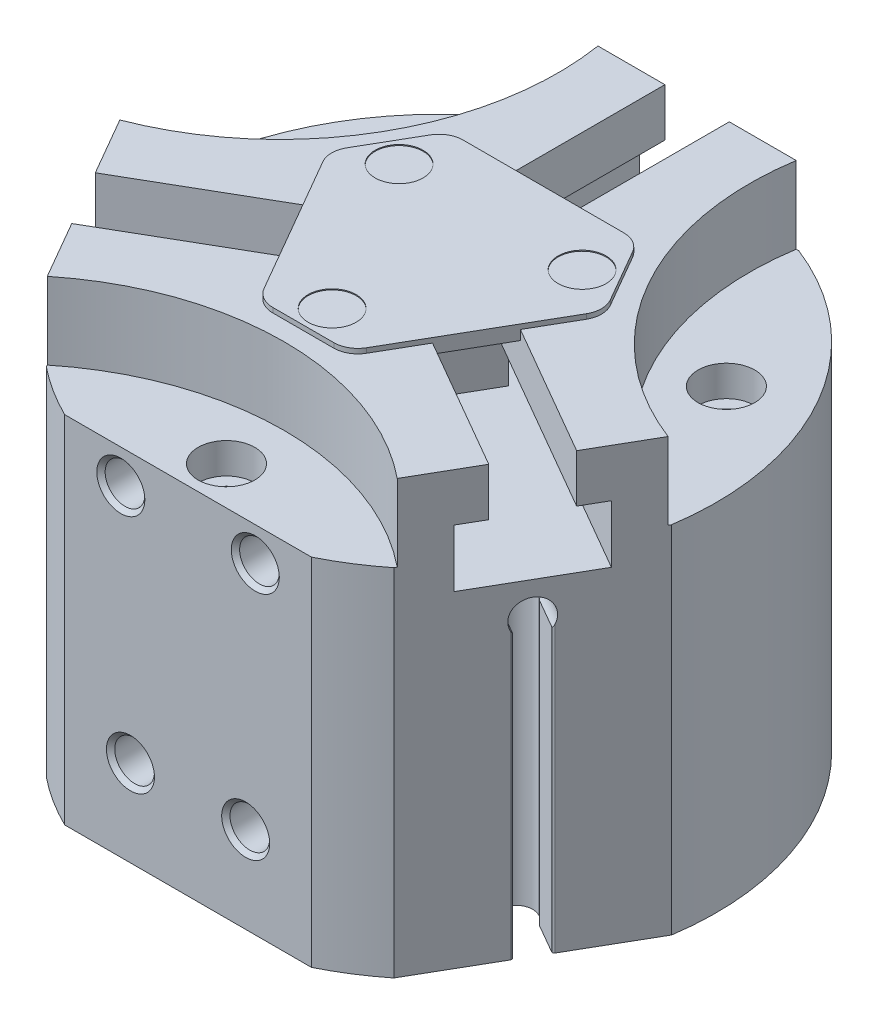
SolidWorks part; units mm, degrees
ref_plane "Front Plane" through (0, 0, 0) normal (0, 0, 1) x (1, 0, 0)
ref_plane "Top Plane" through (0, 0, 0) normal (0, 1, 0) x (1, 0, 0)
ref_plane "Right Plane" through (0, 0, 0) normal (1, 0, 0) x (0, 0, -1)
sketch "Sketch1" plane through (0, 0, 0) normal (0, 1, 0) x (1, 0, 0)
  line L0 (-28.6742, -4.3348) -> (-18.0912, -22.6652)
  line L1 (-12.8452, -26) -> (12.8452, -26)
  line L2 (18.0912, -22.6652) -> (28.6742, -4.3348)
  line L3 (10.583, 27) -> (-10.583, 27)
  arc A0 (-10.583, 27) -> (-28.6742, -4.3348) centre (0, 0) ccw
  arc A1 (-18.0912, -22.6652) -> (-12.8452, -26) centre (0, 0) ccw
  arc A2 (12.8452, -26) -> (18.0912, -22.6652) centre (0, 0) ccw
  arc A3 (28.6742, -4.3348) -> (10.583, 27) centre (0, 0) ccw
extrude "Boss-Extrude1" add sketch "Sketch1" along normal blind 45
ref_plane "Plane1" through (0, 45, 0) normal (0, 1, 0) x (1, 0, 0)
sketch "Sketch2" plane through (0, 45, 0) normal (0, 1, 0) x (1, 0, 0)
  line L0 (-34, -34) -> (34, -34)
  line L1 (34, -34) -> (34, 34)
  line L2 (34, 34) -> (-34, 34)
  line L3 (-34, 34) -> (-34, -34)
  line L4 (-30, -30) -> (-24.8193, -30)
  line L5 (24.8193, -30) -> (30, -30)
  line L6 (30, -30) -> (30, -5.0775)
  line L7 (10.9578, 30) -> (-10.9578, 30)
  line L8 (-30, -5.0775) -> (-30, -30)
  arc A0 (-24.8193, -30) -> (24.8193, -30) centre (0, -45) cw
  arc A1 (30, -5.0775) -> (10.9578, 30) centre (38.9711, 22.5) cw
  arc A2 (-10.9578, 30) -> (-30, -5.0775) centre (-38.9711, 22.5) cw
extrude "Cut-Extrude1" cut sketch "Sketch2" against normal blind 8
ref_plane "Plane2" through (0, 37, 0) normal (0, 1, 0) x (1, 0, 0)
sketch "Sketch3" plane through (0, 0, 0) normal (1, 0, 0) x (0, 0, -1)
  line L0 (-22, 37) -> (-19.05, 37)
  line L1 (-19.05, 37) -> (-19.05, 33.8)
  line L2 (-19.05, 33.8) -> (-20.35, 33.8)
  line L3 (-20.35, 33.8) -> (-20.35, 8)
  line L4 (-20.35, 8) -> (-20.379, 8)
  line L5 (-20.379, 8) -> (-20.379, 0.379)
  line L6 (-20.379, 0.379) -> (-20, 0)
  line L7 (-20, 0) -> (-22, 0)
  line L8 (-22, 0) -> (-22, 37)
  line L9 (-22, 0) -> (-22, 37) construction
revolve "Cut-Revolve1" cut sketch "Sketch3" angle 360 about L9 reverse direction yes
cosmetic thread "Cosmetic Thread1" parameters "D1"=8, "D2"=4
ref_plane "Plane3" through (19.05, 0, 0) normal (1, 0, 0) x (0, 0, -1)
sketch "Sketch4" plane through (19.05, 0, 0) normal (1, 0, 0) x (0, 0, -1)
  line L0 (11, 37) -> (13.95, 37)
  line L1 (13.95, 37) -> (13.95, 33.8)
  line L2 (13.95, 33.8) -> (12.65, 33.8)
  line L3 (12.65, 33.8) -> (12.65, 8)
  line L4 (12.65, 8) -> (12.621, 8)
  line L5 (12.621, 8) -> (12.621, 0.379)
  line L6 (12.621, 0.379) -> (13, 0)
  line L7 (13, 0) -> (11, 0)
  line L8 (11, 0) -> (11, 37)
  line L9 (11, 0) -> (11, 37) construction
revolve "Cut-Revolve2" cut sketch "Sketch4" angle 360 about L9 reverse direction yes
cosmetic thread "Cosmetic Thread2" parameters "D1"=8, "D2"=4
ref_plane "Plane4" through (-19.05, 0, 0) normal (1, 0, 0) x (0, 0, -1)
sketch "Sketch5" plane through (-19.05, 0, 0) normal (1, 0, 0) x (0, 0, -1)
  line L0 (11, 37) -> (13.95, 37)
  line L1 (13.95, 37) -> (13.95, 33.8)
  line L2 (13.95, 33.8) -> (12.65, 33.8)
  line L3 (12.65, 33.8) -> (12.65, 8)
  line L4 (12.65, 8) -> (12.621, 8)
  line L5 (12.621, 8) -> (12.621, 0.379)
  line L6 (12.621, 0.379) -> (13, 0)
  line L7 (13, 0) -> (11, 0)
  line L8 (11, 0) -> (11, 37)
  line L9 (11, 0) -> (11, 37) construction
revolve "Cut-Revolve3" cut sketch "Sketch5" angle 360 about L9 reverse direction yes
cosmetic thread "Cosmetic Thread3" parameters "D1"=8, "D2"=4
sketch "Sketch6" plane through (0, 0, 0) normal (0, 1, 0) x (1, 0, 0)
  line L0 (-1.9, 28) -> (-1.9, 27)
  line L1 (-1.9, 27) -> (-1.7, 27)
  line L2 (-1.5, 26.8) -> (-1.5, 23.3)
  line L3 (-1.6807, 23.1009) -> (-1.7, 23.0991)
  line L4 (-1.8798, 22.8816) -> (-1.7924, 21.9345)
  line L5 (1.7924, 21.9345) -> (1.8798, 22.8816)
  line L6 (1.7, 23.0991) -> (1.6807, 23.1009)
  line L7 (1.5, 23.3) -> (1.5, 26.8)
  line L8 (1.7, 27) -> (1.9, 27)
  line L9 (1.9, 27) -> (1.9, 28)
  line L10 (1.9, 28) -> (-1.9, 28)
  arc A0 (-1.7, 27) -> (-1.5, 26.8) centre (-1.7, 26.8) cw
  arc A1 (-1.5, 23.3) -> (-1.6807, 23.1009) centre (-1.7, 23.3) cw
  arc A2 (-1.7, 23.0991) -> (-1.8798, 22.8816) centre (-1.6807, 22.9) ccw
  arc A3 (-1.7924, 21.9345) -> (1.7924, 21.9345) centre (0, 22.1) ccw
  arc A4 (1.8798, 22.8816) -> (1.7, 23.0991) centre (1.6807, 22.9) ccw
  arc A5 (1.6807, 23.1009) -> (1.5, 23.3) centre (1.7, 23.3) cw
  arc A6 (1.5, 26.8) -> (1.7, 27) centre (1.7, 26.8) cw
extrude "Cut-Extrude2" cut sketch "Sketch6" along normal blind 30.5
sketch "Sketch7" plane through (0, 0, 0) normal (0, 1, 0) x (1, 0, 0)
  line L0 (-25.1987, -12.3546) -> (-23.2987, -15.6454)
  line L1 (-23.2987, -15.6454) -> (-22.4327, -15.1454)
  line L2 (-22.4327, -15.1454) -> (-22.5327, -14.9722)
  line L3 (-22.4595, -14.699) -> (-19.4284, -12.949)
  line L4 (-19.1656, -13.006) -> (-19.1544, -13.0217)
  line L5 (-18.8761, -13.0688) -> (-18.0996, -12.5195)
  line L6 (-19.892, -9.415) -> (-20.756, -9.8128)
  line L7 (-20.8544, -10.0773) -> (-20.8464, -10.0949)
  line L8 (-20.9284, -10.351) -> (-23.9595, -12.101)
  line L9 (-24.2327, -12.0278) -> (-24.3327, -11.8546)
  line L10 (-24.3327, -11.8546) -> (-25.1987, -12.3546)
  arc A0 (-22.5327, -14.9722) -> (-22.4595, -14.699) centre (-22.3595, -14.8722) cw
  arc A1 (-19.4284, -12.949) -> (-19.1656, -13.006) centre (-19.3284, -13.1222) cw
  arc A2 (-19.1544, -13.0217) -> (-18.8761, -13.0688) centre (-18.9916, -12.9055) ccw
  arc A3 (-18.0996, -12.5195) -> (-19.892, -9.415) centre (-19.1392, -11.05) ccw
  arc A4 (-20.756, -9.8128) -> (-20.8544, -10.0773) centre (-20.6723, -9.9945) ccw
  arc A5 (-20.8464, -10.0949) -> (-20.9284, -10.351) centre (-21.0284, -10.1778) cw
  arc A6 (-23.9595, -12.101) -> (-24.2327, -12.0278) centre (-24.0595, -11.9278) cw
extrude "Cut-Extrude3" cut sketch "Sketch7" along normal blind 30.5
sketch "Sketch8" plane through (0, 0, 0) normal (0, 1, 0) x (1, 0, 0)
  line L0 (18.0996, -12.5195) -> (18.8761, -13.0688)
  line L1 (19.1544, -13.0217) -> (19.1656, -13.006)
  line L2 (19.4284, -12.949) -> (22.4595, -14.699)
  line L3 (22.5327, -14.9722) -> (22.4327, -15.1454)
  line L4 (22.4327, -15.1454) -> (23.2987, -15.6454)
  line L5 (23.2987, -15.6454) -> (25.1987, -12.3546)
  line L6 (25.1987, -12.3546) -> (24.3327, -11.8546)
  line L7 (24.3327, -11.8546) -> (24.2327, -12.0278)
  line L8 (23.9595, -12.101) -> (20.9284, -10.351)
  line L9 (20.8464, -10.0949) -> (20.8544, -10.0773)
  line L10 (20.756, -9.8128) -> (19.892, -9.415)
  arc A0 (19.892, -9.415) -> (18.0996, -12.5195) centre (19.1392, -11.05) ccw
  arc A1 (18.8761, -13.0688) -> (19.1544, -13.0217) centre (18.9916, -12.9055) ccw
  arc A2 (19.1656, -13.006) -> (19.4284, -12.949) centre (19.3284, -13.1222) cw
  arc A3 (22.4595, -14.699) -> (22.5327, -14.9722) centre (22.3595, -14.8722) cw
  arc A4 (24.2327, -12.0278) -> (23.9595, -12.101) centre (24.0595, -11.9278) cw
  arc A5 (20.9284, -10.351) -> (20.8464, -10.0949) centre (21.0284, -10.1778) cw
  arc A6 (20.8544, -10.0773) -> (20.756, -9.8128) centre (20.6723, -9.9945) ccw
extrude "Cut-Extrude4" cut sketch "Sketch8" along normal blind 30.5
ref_plane "Plane5" through (0, 30.5, 0) normal (0, 1, 0) x (1, 0, 0)
sketch "Sketch9" plane through (0, 30.5, 0) normal (0, 1, 0) x (1, 0, 0)
  line L0 (-1.7924, 21.9345) -> (-1.9, 23.1)
  line L1 (-1.9, 23.1) -> (-1.9, 27)
  line L2 (-1.9, 27) -> (0, 27)
  line L3 (0, 27) -> (0, 20.3)
  line L4 (0, 27) -> (0, 20.3) construction
  arc A0 (0, 20.3) -> (-1.7924, 21.9345) centre (0, 22.1) cw
revolve "Cut-Revolve4" cut sketch "Sketch9" angle 360 about L4 reverse direction yes
sketch "Sketch10" plane through (0, 30.5, 0) normal (0, 1, 0) x (1, 0, 0)
  line L0 (-18.0996, -12.5195) -> (-19.0552, -13.1954)
  line L1 (-19.0552, -13.1954) -> (-22.4327, -15.1454)
  line L2 (-22.4327, -15.1454) -> (-23.3827, -13.5)
  line L3 (-23.3827, -13.5) -> (-17.5803, -10.15)
  line L4 (-23.3827, -13.5) -> (-17.5803, -10.15) construction
  arc A0 (-17.5803, -10.15) -> (-18.0996, -12.5195) centre (-19.1392, -11.05) cw
revolve "Cut-Revolve5" cut sketch "Sketch10" angle 360 about L4 reverse direction yes
sketch "Sketch11" plane through (0, 30.5, 0) normal (0, 1, 0) x (1, 0, 0)
  line L0 (19.892, -9.415) -> (20.9552, -9.9046)
  line L1 (20.9552, -9.9046) -> (24.3327, -11.8546)
  line L2 (24.3327, -11.8546) -> (23.3827, -13.5)
  line L3 (23.3827, -13.5) -> (17.5803, -10.15)
  line L4 (23.3827, -13.5) -> (17.5803, -10.15) construction
  arc A0 (17.5803, -10.15) -> (19.892, -9.415) centre (19.1392, -11.05) cw
revolve "Cut-Revolve6" cut sketch "Sketch11" angle 360 about L4 reverse direction yes
hole_wizard "Hole1" positions "Sketch13" profile "Sketch12" legacy
sketch "Sketch13" plane through (0, 0, 0) normal (0, -1, 0) x (-1, 0, 0)
  point P0 (-22.5, 0)
sketch "Sketch12" plane through (22.5, 0, 0) normal (1, 0, 0) x (0, 0, -1)
  line L0 (0, 0) -> (0, 5)
  line L1 (0, 5) -> (1.5, 5)
  line L2 (1.5, 5) -> (1.5, 0)
  line L3 (1.5, 0) -> (0, 0)
  line L4 (0, 110) -> (0, -10) construction
  dimension "Diameter" = 3
  dimension "Depth" = 5
hole_wizard "Hole2" positions "Sketch15" profile "Sketch14" legacy
sketch "Sketch15" plane through (0, 0, 0) normal (0, -1, 0) x (-1, 0, 0)
  point P0 (22.5, 0)
sketch "Sketch14" plane through (-22.5, 0, 0) normal (1, 0, 0) x (0, 0, -1)
  line L0 (0, 0) -> (0, 5)
  line L1 (0, 5) -> (1.5, 5)
  line L2 (1.5, 5) -> (1.5, 0)
  line L3 (1.5, 0) -> (0, 0)
  line L4 (0, 110) -> (0, -10) construction
  dimension "Diameter" = 3
  dimension "Depth" = 5
ref_plane "Plane6" through (7.5, 0, 0) normal (1, 0, 0) x (0, 0, -1)
hole_wizard "Hole3" positions "Sketch17" profile "Sketch16" legacy
sketch "Sketch17" plane through (0, 0, 0) normal (0, -1, 0) x (-1, 0, 0)
  point P0 (-7.5, -18.5)
sketch "Sketch16" plane through (7.5, 0, 18.5) normal (1, 0, 0) x (0, 0, -1)
  line L0 (0, 0) -> (0, 9.7099)
  line L1 (0, 9.7099) -> (1.2295, 9)
  line L2 (1.2295, 9) -> (1.2295, 0.2705)
  line L3 (1.2295, 0.2705) -> (1.5, 0)
  line L4 (1.5, 0) -> (0, 0)
  line L5 (0, -14.3089) -> (0, 102.4216) construction
  line L6 (0, 9.7099) -> (-1.2295, 9) construction
  line L7 (-1.2295, 0.2705) -> (-1.5, 0) construction
  dimension "Diameter" = 2.459
  dimension "Depth" = 9
  dimension "C-Sink Diameter" = 3
  dimension "C-Sink Angle" = 90
  dimension "Drill Angle" = 120
cosmetic thread "Cosmetic Thread4" parameters "D1"=3, "D2"=3
ref_plane "Plane7" through (-7.5, 0, 0) normal (1, 0, 0) x (0, 0, -1)
hole_wizard "Hole4" positions "Sketch19" profile "Sketch18" legacy
sketch "Sketch19" plane through (0, 0, 0) normal (0, -1, 0) x (-1, 0, 0)
  point P0 (7.5, -18.5)
sketch "Sketch18" plane through (-7.5, 0, 18.5) normal (1, 0, 0) x (0, 0, -1)
  line L0 (0, 0) -> (0, 9.7099)
  line L1 (0, 9.7099) -> (1.2295, 9)
  line L2 (1.2295, 9) -> (1.2295, 0.2705)
  line L3 (1.2295, 0.2705) -> (1.5, 0)
  line L4 (1.5, 0) -> (0, 0)
  line L5 (0, -14.3089) -> (0, 102.4216) construction
  line L6 (0, 9.7099) -> (-1.2295, 9) construction
  line L7 (-1.2295, 0.2705) -> (-1.5, 0) construction
  dimension "Diameter" = 2.459
  dimension "Depth" = 9
  dimension "C-Sink Diameter" = 3
  dimension "C-Sink Angle" = 90
  dimension "Drill Angle" = 120
cosmetic thread "Cosmetic Thread5" parameters "D1"=3, "D2"=3
ref_plane "Plane8" through (-6, 0, 0) normal (1, 0, 0) x (0, 0, -1)
sketch "Sketch20" plane through (-6, 0, 0) normal (1, 0, 0) x (0, 0, -1)
  line L0 (-26, 9) -> (-26, 11.5)
  line L1 (-26, 11.5) -> (-25.567, 11.067)
  line L2 (-25.567, 11.067) -> (-19.5, 11.067)
  line L3 (-19.5, 11.067) -> (-18.3066, 9)
  line L4 (-18.3066, 9) -> (-26, 9)
  line L5 (-18.3066, 9) -> (-26, 9) construction
revolve "Cut-Revolve7" cut sketch "Sketch20" angle 360 about L5 reverse direction yes
cosmetic thread "Cosmetic Thread6" parameters "D1"=5, "D2"=5
ref_plane "Plane9" through (6, 0, 0) normal (1, 0, 0) x (0, 0, -1)
sketch "Sketch21" plane through (6, 0, 0) normal (1, 0, 0) x (0, 0, -1)
  line L0 (-26, 9) -> (-26, 11.5)
  line L1 (-26, 11.5) -> (-25.567, 11.067)
  line L2 (-25.567, 11.067) -> (-19.5, 11.067)
  line L3 (-19.5, 11.067) -> (-18.3066, 9)
  line L4 (-18.3066, 9) -> (-26, 9)
  line L5 (-18.3066, 9) -> (-26, 9) construction
revolve "Cut-Revolve8" cut sketch "Sketch21" angle 360 about L5 reverse direction yes
cosmetic thread "Cosmetic Thread7" parameters "D1"=5, "D2"=5
ref_plane "Plane10" through (7, 0, 0) normal (1, 0, 0) x (0, 0, -1)
sketch "Sketch22" plane through (7, 0, 0) normal (1, 0, 0) x (0, 0, -1)
  line L0 (-26, 33.5) -> (-26, 36)
  line L1 (-26, 36) -> (-25.567, 35.567)
  line L2 (-25.567, 35.567) -> (-19.5, 35.567)
  line L3 (-19.5, 35.567) -> (-18.3066, 33.5)
  line L4 (-18.3066, 33.5) -> (-26, 33.5)
  line L5 (-18.3066, 33.5) -> (-26, 33.5) construction
revolve "Cut-Revolve9" cut sketch "Sketch22" angle 360 about L5 reverse direction yes
cosmetic thread "Cosmetic Thread8" parameters "D1"=5, "D2"=5
ref_plane "Plane11" through (-7, 0, 0) normal (1, 0, 0) x (0, 0, -1)
sketch "Sketch23" plane through (-7, 0, 0) normal (1, 0, 0) x (0, 0, -1)
  line L0 (-26, 33.5) -> (-26, 36)
  line L1 (-26, 36) -> (-25.567, 35.567)
  line L2 (-25.567, 35.567) -> (-19.5, 35.567)
  line L3 (-19.5, 35.567) -> (-18.3066, 33.5)
  line L4 (-18.3066, 33.5) -> (-26, 33.5)
  line L5 (-18.3066, 33.5) -> (-26, 33.5) construction
revolve "Cut-Revolve10" cut sketch "Sketch23" angle 360 about L5 reverse direction yes
cosmetic thread "Cosmetic Thread9" parameters "D1"=5, "D2"=5
hole_wizard "Hole5" positions "Sketch25" profile "Sketch24" legacy
sketch "Sketch25" plane through (0, 0, 0) normal (0, -1, 0) x (-1, 0, 0)
  point P0 (0, 0)
sketch "Sketch24" plane through (0, 0, 0) normal (1, 0, 0) x (0, 0, -1)
  line L0 (0, 0) -> (0, 2)
  line L1 (0, 2) -> (12.5, 2)
  line L2 (12.5, 2) -> (12.5, 0)
  line L3 (12.5, 0) -> (0, 0)
  line L4 (0, 110) -> (0, -10) construction
  dimension "Diameter" = 25
  dimension "Depth" = 2
ref_plane "Plane12" through (0, 0, -27) normal (0, 0, 1) x (1, 0, 0)
sketch "Sketch26" plane through (0, 0, -27) normal (0, 0, 1) x (1, 0, 0)
  line L0 (-6, 34) -> (6, 34)
  line L1 (6, 34) -> (6, 40)
  line L2 (6, 40) -> (3.35, 40)
  line L3 (3.35, 40) -> (3.35, 46)
  line L4 (3.35, 46) -> (-3.35, 46)
  line L5 (-3.35, 46) -> (-3.35, 40)
  line L6 (-3.35, 40) -> (-6, 40)
  line L7 (-6, 40) -> (-6, 34)
extrude "Cut-Extrude5" cut sketch "Sketch26" along normal blind 16
sketch "Sketch27" plane through (0, 0, -27) normal (0, 0, 1) x (1, 0, 0)
  line L0 (-6, 34) -> (6, 34)
  line L1 (6, 34) -> (6, 40)
  line L2 (6, 40) -> (3.35, 40)
  line L3 (3.35, 40) -> (3.35, 44)
  line L4 (3.35, 44) -> (-3.35, 44)
  line L5 (-3.35, 44) -> (-3.35, 40)
  line L6 (-3.35, 40) -> (-6, 40)
  line L7 (-6, 40) -> (-6, 34)
extrude "Cut-Extrude6" cut sketch "Sketch27" along normal blind 24.3
ref_plane "Plane13" through (0, 0, 0) normal (0.866, 0, 0.5) x (0.5, 0, -0.866)
ref_plane "Plane14" through (23.3827, 0, 13.5) normal (0.866, 0, 0.5) x (0.5, 0, -0.866)
sketch "Sketch28" plane through (23.3827, 0, 13.5) normal (0.866, 0, 0.5) x (0.5, 0, -0.866)
  line L0 (-6, 34) -> (6, 34)
  line L1 (6, 34) -> (6, 40)
  line L2 (6, 40) -> (3.35, 40)
  line L3 (3.35, 40) -> (3.35, 46)
  line L4 (3.35, 46) -> (-3.35, 46)
  line L5 (-3.35, 46) -> (-3.35, 40)
  line L6 (-3.35, 40) -> (-6, 40)
  line L7 (-6, 40) -> (-6, 34)
extrude "Cut-Extrude7" cut sketch "Sketch28" against normal blind 16
sketch "Sketch29" plane through (23.3827, 0, 13.5) normal (0.866, 0, 0.5) x (0.5, 0, -0.866)
  line L0 (-6, 34) -> (6, 34)
  line L1 (6, 34) -> (6, 40)
  line L2 (6, 40) -> (3.35, 40)
  line L3 (3.35, 40) -> (3.35, 44)
  line L4 (3.35, 44) -> (-3.35, 44)
  line L5 (-3.35, 44) -> (-3.35, 40)
  line L6 (-3.35, 40) -> (-6, 40)
  line L7 (-6, 40) -> (-6, 34)
extrude "Cut-Extrude8" cut sketch "Sketch29" against normal blind 24.3
ref_plane "Plane15" through (0, 0, 0) normal (0.866, 0, -0.5) x (-0.5, 0, -0.866)
ref_plane "Plane16" through (-23.3827, 0, 13.5) normal (0.866, 0, -0.5) x (-0.5, 0, -0.866)
sketch "Sketch30" plane through (-23.3827, 0, 13.5) normal (0.866, 0, -0.5) x (-0.5, 0, -0.866)
  line L0 (-6, 34) -> (6, 34)
  line L1 (6, 34) -> (6, 40)
  line L2 (6, 40) -> (3.35, 40)
  line L3 (3.35, 40) -> (3.35, 46)
  line L4 (3.35, 46) -> (-3.35, 46)
  line L5 (-3.35, 46) -> (-3.35, 40)
  line L6 (-3.35, 40) -> (-6, 40)
  line L7 (-6, 40) -> (-6, 34)
extrude "Cut-Extrude9" cut sketch "Sketch30" along normal blind 16
sketch "Sketch31" plane through (-23.3827, 0, 13.5) normal (0.866, 0, -0.5) x (-0.5, 0, -0.866)
  line L0 (-6, 34) -> (6, 34)
  line L1 (6, 34) -> (6, 40)
  line L2 (6, 40) -> (3.35, 40)
  line L3 (3.35, 40) -> (3.35, 44)
  line L4 (3.35, 44) -> (-3.35, 44)
  line L5 (-3.35, 44) -> (-3.35, 40)
  line L6 (-3.35, 40) -> (-6, 40)
  line L7 (-6, 40) -> (-6, 34)
extrude "Cut-Extrude10" cut sketch "Sketch31" along normal blind 24.3
ref_plane "Plane17" through (0, 45, 0) normal (0, 1, 0) x (1, 0, 0)
sketch "Sketch32" plane through (0, 45, 0) normal (0, 1, 0) x (1, 0, 0)
  line L0 (-13.7121, 1.75) -> (-5.3405, -12.75)
  line L1 (-3.1754, -14) -> (3.1754, -14)
  line L2 (5.3405, -12.75) -> (13.7121, 1.75)
  line L3 (13.7121, 4.25) -> (10.5366, 9.75)
  line L4 (8.3716, 11) -> (-8.3716, 11)
  line L5 (-10.5366, 9.75) -> (-13.7121, 4.25)
  arc A0 (-13.7121, 4.25) -> (-13.7121, 1.75) centre (-11.547, 3) ccw
  arc A1 (-5.3405, -12.75) -> (-3.1754, -14) centre (-3.1754, -11.5) ccw
  arc A2 (3.1754, -14) -> (5.3405, -12.75) centre (3.1754, -11.5) ccw
  arc A3 (13.7121, 1.75) -> (13.7121, 4.25) centre (11.547, 3) ccw
  arc A4 (10.5366, 9.75) -> (8.3716, 11) centre (8.3716, 8.5) ccw
  arc A5 (-8.3716, 11) -> (-10.5366, 9.75) centre (-8.3716, 8.5) ccw
extrude "Boss-Extrude2" add sketch "Sketch32" along normal blind 0.5
ref_plane "Plane18" through (0, 45.5, 0) normal (0, 1, 0) x (1, 0, 0)
sketch "Sketch33" plane through (0, 45.5, 0) normal (0, 1, 0) x (1, 0, 0)
  circle A0 centre (0, -11) radius 2.5
extrude "Cut-Extrude11" cut sketch "Sketch33" against normal blind 0.1
sketch "Sketch34" plane through (0, 45.5, 0) normal (0, 1, 0) x (1, 0, 0)
  circle A0 centre (9.5263, 5.5) radius 2.5
extrude "Cut-Extrude12" cut sketch "Sketch34" against normal blind 0.1
sketch "Sketch35" plane through (0, 45.5, 0) normal (0, 1, 0) x (1, 0, 0)
  circle A0 centre (-9.5263, 5.5) radius 2.5
extrude "Cut-Extrude13" cut sketch "Sketch35" against normal blind 0.1
ref_plane "Plane19" through (0, 68, 0) normal (0, 1, 0) x (1, 0, 0)
ref_plane "Plane20" through (0, 0, 26) normal (0, 0, 1) x (1, 0, 0)
ref_plane "Plane21" through (0, 0, 0) normal (0, 1, 0) x (1, 0, 0)
ref_plane "SCH1 1 XY" through (0, 0, 26) normal (0, 0, 1) x (1, 0, 0)
ref_plane "SCH1 1 XZ" through (0, 33.5, 0) normal (0, -1, 0) x (-1, 0, 0)
ref_plane "SCH1 1 YZ" through (-7, 0, 0) normal (1, 0, 0) x (0, 0, -1)
ref_axis "SCH1 1 X" through (-80.9, 33.5, 26) along (1, 0, 0)
ref_axis "SCH1 1 Y" through (-7, -50, 26) along (0, 1, 0)
ref_axis "SCH1 1 Z" through (-7, 33.5, 80.9) along (0, 0, -1)
sketch3d "SCH1 1"
  point P0 (-7, 33.5, 26)
ref_plane "SCH1 2 XY" through (0, 0, 26) normal (0, 0, 1) x (1, 0, 0)
ref_plane "SCH1 2 XZ" through (0, 33.5, 0) normal (0, -1, 0) x (-1, 0, 0)
ref_plane "SCH1 2 YZ" through (7, 0, 0) normal (1, 0, 0) x (0, 0, -1)
ref_axis "SCH1 2 X" through (-80.9, 33.5, 26) along (1, 0, 0)
ref_axis "SCH1 2 Y" through (7, -50, 26) along (0, 1, 0)
ref_axis "SCH1 2 Z" through (7, 33.5, 80.9) along (0, 0, -1)
sketch3d "SCH1 2"
  point P0 (7, 33.5, 26)
ref_plane "SCH2 1 XY" through (0, 0, 0) normal (0, -1, 0) x (-1, 0, 0)
ref_plane "SCH2 1 XZ" through (0, 0, 18.5) normal (0, 0, -1) x (-1, 0, 0)
ref_plane "SCH2 1 YZ" through (-7.5, 0, 0) normal (1, 0, 0) x (0, 0, -1)
ref_axis "SCH2 1 X" through (-80.9, 0, 18.5) along (1, 0, 0)
ref_axis "SCH2 1 Y" through (-7.5, 0, -50) along (0, 0, 1)
ref_axis "SCH2 1 Z" through (-7.5, -50, 18.5) along (0, 1, 0)
sketch3d "SCH2 1"
  point P0 (-7.5, 0, 18.5)
ref_plane "SCH2 2 XY" through (0, 0, 0) normal (0, -1, 0) x (-1, 0, 0)
ref_plane "SCH2 2 XZ" through (0, 0, 18.5) normal (0, 0, -1) x (-1, 0, 0)
ref_plane "SCH2 2 YZ" through (7.5, 0, 0) normal (1, 0, 0) x (0, 0, -1)
ref_axis "SCH2 2 X" through (-80.9, 0, 18.5) along (1, 0, 0)
ref_axis "SCH2 2 Y" through (7.5, 0, -50) along (0, 0, 1)
ref_axis "SCH2 2 Z" through (7.5, -50, 18.5) along (0, 1, 0)
sketch3d "SCH2 2"
  point P0 (7.5, 0, 18.5)
ref_plane "TO_DUMMY XY" through (0, 0, 0) normal (0, 0, 1) x (1, 0, 0)
ref_plane "TO_DUMMY XZ" through (0, 0, 0) normal (0, -1, 0) x (-1, 0, 0)
ref_plane "TO_DUMMY YZ" through (0, 0, 0) normal (1, 0, 0) x (0, 0, -1)
ref_axis "TO_DUMMY X" through (-80.9, 0, 0) along (1, 0, 0)
ref_axis "TO_DUMMY Y" through (0, -50, 0) along (0, 1, 0)
ref_axis "TO_DUMMY Z" through (0, 0, 80.9) along (0, 0, -1)
sketch3d "TO_DUMMY"
  point P0 (0, 0, 0)
ref_plane "TO_JAW XY" through (0, 0, -27) normal (0, 0, 1) x (1, 0, 0)
ref_plane "TO_JAW XZ" through (0, 34, 0) normal (0, -1, 0) x (-1, 0, 0)
ref_plane "TO_JAW YZ" through (0, 0, 0) normal (1, 0, 0) x (0, 0, -1)
ref_axis "TO_JAW X" through (-80.9, 34, -27) along (1, 0, 0)
ref_axis "TO_JAW Y" through (0, -50, -27) along (0, 1, 0)
ref_axis "TO_JAW Z" through (0, 34, 80.9) along (0, 0, -1)
sketch3d "TO_JAW"
  point P0 (0, 34, -27)
ref_plane "TO_JAW2 XY" through (23.3827, 0, 13.5) normal (0.866, 0, 0.5) x (0.5, 0, -0.866)
ref_plane "TO_JAW2 XZ" through (0, 34, 0) normal (0, -1, 0) x (-1, 0, 0)
ref_plane "TO_JAW2 YZ" through (0, 0, 0) normal (0.5, 0, -0.866) x (-0.866, 0, -0.5)
ref_axis "TO_JAW2 X" through (-17.0673, 34, 83.5615) along (0.5, 0, -0.866)
ref_axis "TO_JAW2 Y" through (23.3827, -50, 13.5) along (0, 1, 0)
ref_axis "TO_JAW2 Z" through (70.0615, 34, 40.45) along (-0.866, 0, -0.5)
sketch3d "TO_JAW2"
  point P0 (23.3827, 34, 13.5)
ref_plane "TO_JAW3 XY" through (-23.3827, 0, 13.5) normal (0.866, 0, -0.5) x (-0.5, 0, -0.866)
ref_plane "TO_JAW3 XZ" through (0, 34, 0) normal (0, -1, 0) x (-1, 0, 0)
ref_plane "TO_JAW3 YZ" through (0, 0, 0) normal (-0.5, 0, -0.866) x (-0.866, 0, 0.5)
ref_axis "TO_JAW3 X" through (17.0673, 34, 83.5615) along (-0.5, 0, -0.866)
ref_axis "TO_JAW3 Y" through (-23.3827, -50, 13.5) along (0, 1, 0)
ref_axis "TO_JAW3 Z" through (70.0615, 34, -40.45) along (-0.866, 0, 0.5)
sketch3d "TO_JAW3"
  point P0 (-23.3827, 34, 13.5)
other "Freeze***"
